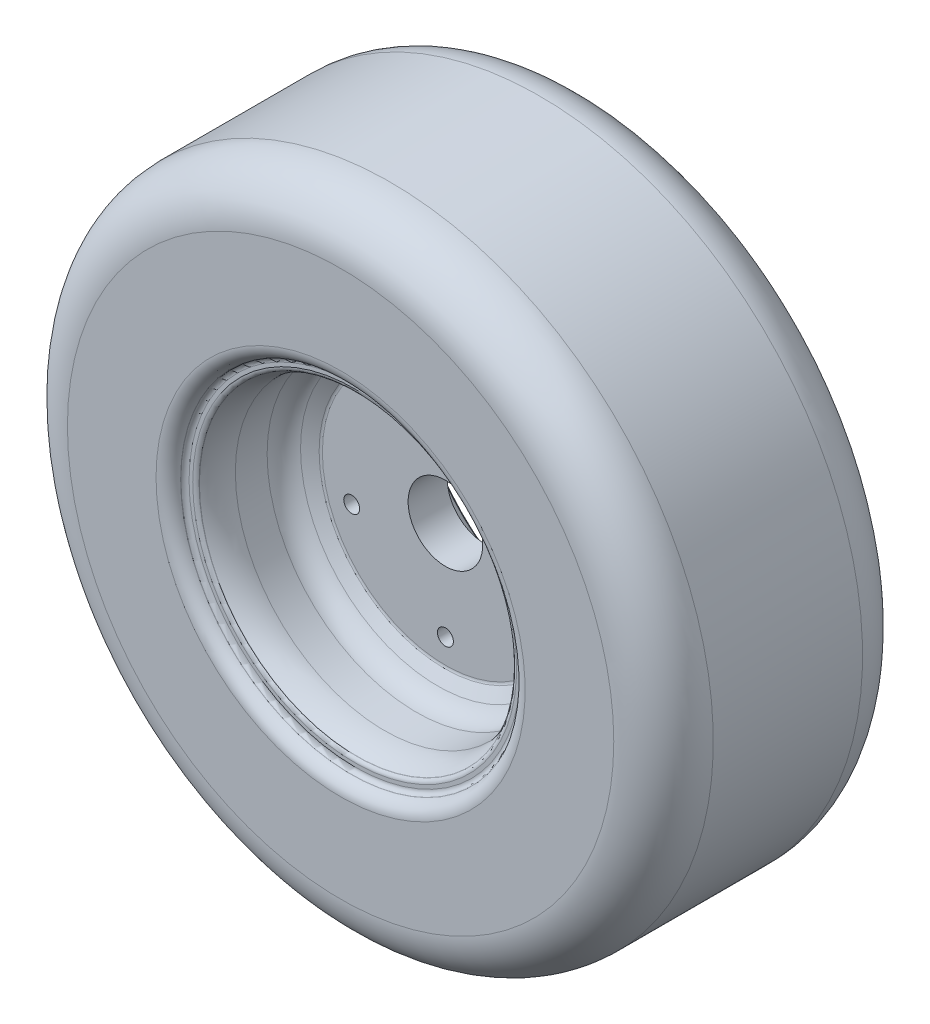
SolidWorks part; units mm, degrees
material "Rubber"
ref_plane "Front Plane" through (0, 0, 0) normal (0, 0, 1) x (1, 0, 0)
ref_plane "Top Plane" through (0, 0, 0) normal (0, 1, 0) x (1, 0, 0)
ref_plane "Right Plane" through (0, 0, 0) normal (1, 0, 0) x (0, 0, -1)
sketch "Sketch1" plane through (0, 0, 0) normal (1, 0, 0) x (0, 0, -1)
  line L0 (0, 164.846) -> (0, -164.846) construction
  line L1 (76.2, 0) -> (-76.2, 0) construction
  line L2 (10, 0) -> (10, 62.7965)
  line L3 (24.13, 164.846) -> (0, 164.846)
  line L4 (63.5, 139.446) -> (63.5, 94.2121)
  line L5 (58.1976, 86.9531) -> (58.1075, 86.9243)
  line L6 (56.34, 84.5046) -> (56.34, 82.6394)
  line L7 (55.2089, 80.526) -> (55.1189, 80.4659)
  line L8 (41.0295, 76.2) -> (24.8106, 76.2)
  line L9 (13.9205, 70.0341) -> (10.362, 64.1033)
  line L10 (-24.13, 164.846) -> (0, 164.846)
  line L11 (24.13, 164.846) -> (38.1, 164.846)
  line L13 (40.18, 161.0098) -> (-40.18, 161.0098)
  line L14 (60.5, 140.6898) -> (60.5, 100.846)
  line L15 (40.18, 80.526) -> (-40.18, 80.526)
  line L16 (-60.5, 140.6898) -> (-60.5, 100.846)
  line L24 (-24.13, 164.846) -> (-38.1, 164.846)
  line L26 (-13.9205, 70.0341) -> (-10.362, 64.1033)
  line L27 (-41.0295, 76.2) -> (-24.8106, 76.2)
  line L28 (-55.2089, 80.526) -> (-55.1189, 80.4659)
  line L29 (-56.34, 84.5046) -> (-56.34, 82.6394)
  line L30 (-58.1976, 86.9531) -> (-58.1075, 86.9243)
  line L31 (-63.5, 139.446) -> (-63.5, 94.2121)
  line L32 (-10, 0) -> (-10, 62.7965)
  line L33 (10, 0) -> (-10, 0)
  arc A0 (38.1, 164.846) -> (63.5, 139.446) centre (38.1, 139.446) cw
  arc A1 (63.5, 94.2121) -> (58.1976, 86.9531) centre (55.88, 94.2121) cw
  arc A2 (58.1075, 86.9243) -> (56.34, 84.5046) centre (58.88, 84.5046) ccw
  arc A3 (56.34, 82.6394) -> (55.2089, 80.526) centre (53.8, 82.6394) cw
  arc A4 (55.1189, 80.4659) -> (41.0295, 76.2) centre (41.0295, 101.6) cw
  arc A5 (24.8106, 76.2) -> (13.9205, 70.0341) centre (24.8106, 63.5) ccw
  arc A6 (10.362, 64.1033) -> (10, 62.7965) centre (12.54, 62.7965) ccw
  arc A7 (-10.362, 64.1033) -> (-10, 62.7965) centre (-12.54, 62.7965) cw
  arc A8 (-24.8106, 76.2) -> (-13.9205, 70.0341) centre (-24.8106, 63.5) cw
  arc A9 (-55.1189, 80.4659) -> (-41.0295, 76.2) centre (-41.0295, 101.6) ccw
  arc A10 (-56.34, 82.6394) -> (-55.2089, 80.526) centre (-53.8, 82.6394) ccw
  arc A11 (-58.1075, 86.9243) -> (-56.34, 84.5046) centre (-58.88, 84.5046) cw
  arc A12 (-63.5, 94.2121) -> (-58.1976, 86.9531) centre (-55.88, 94.2121) ccw
  arc A13 (-38.1, 164.846) -> (-63.5, 139.446) centre (-38.1, 139.446) ccw
  arc A14 (-40.18, 80.526) -> (-60.5, 100.846) centre (-40.18, 100.846) cw
  arc A15 (60.5, 100.846) -> (40.18, 80.526) centre (40.18, 100.846) cw
  arc A16 (40.18, 161.0098) -> (60.5, 140.6898) centre (40.18, 140.6898) cw
  arc A17 (-40.18, 161.0098) -> (-60.5, 140.6898) centre (-40.18, 140.6898) ccw
  point P15 (63.5, 164.846)
  point P18 (63.5, 88.646)
  point P21 (56.34, 86.36)
  point P24 (56.34, 81.28)
  point P27 (48.72, 76.2)
  point P30 (17.62, 76.2)
  point P33 (10, 63.5)
  dimension "D3" = 76.2
  dimension "D13" = 25.4
  dimension "D14" = 7.62
  dimension "D15" = 2.54
  dimension "D16" = 2.54
  dimension "D17" = 25.4
  dimension "D18" = 12.7
  dimension "D19" = 2.54
  dimension "D20" = 20.32
  dimension "D1" = 329.692
  dimension "D2" = 152.4
  dimension "D4" = 63.5
  dimension "D5" = 127
  dimension "D6" = 10
  dimension "D7" = 7.62
  dimension "D8" = 12.7
  dimension "D9" = 5.08
  dimension "D10" = 7.62
  dimension "D11" = 5.08
  dimension "D12" = 7.16
  dimension "D21" = 3
  dimension "D22" = 3
revolve "Revolve2" add sketch "Sketch1" angle 360 about L1
sketch "Sketch3" plane through (0, 0, -10) normal (0, 0, -1) x (-1, 0, 0)
  line L0 (50.292, 0) -> (-50.292, 0) construction
  line L1 (0, 50.292) -> (0, -50.292) construction
  line L2 (0, 0) -> (47.8305, -15.5411) construction
  circle A0 centre (0, 0) radius 50.292 construction
  circle A1 centre (0, -50.292) radius 4.064
  circle A2 centre (-47.8305, -15.5411) radius 4.064
  circle A3 centre (-29.5609, 40.6871) radius 4.064
  circle A4 centre (29.5609, 40.6871) radius 4.064
  circle A5 centre (47.8305, -15.5411) radius 4.064
  circle A6 centre (0, 0) radius 19.05
  point P20 (0, 0)
  dimension "D1" = 100.584
  dimension "D2" = 8.128
  dimension "D3" = 5
  dimension "D5" = 50.292
  dimension "D6" = 38.1
  dimension "D4" = 72
extrude "Cut-Extrude1" cut sketch "Sketch3" against normal through all both and the other way through all
ref_axis "Axis1" [suppressed] through (0, 0, 10) along (0, 0, -1)
ref_plane "Plane1" through (0, 167.64, 0) normal (0, 1, 0) x (1, 0, 0)
sketch "Sketch4" plane through (0, 167.64, 0) normal (0, 1, 0) x (1, 0, 0)
  line L0 (-164.846, -38.1) -> (164.846, -38.1) construction
  line L1 (-164.846, 38.1) -> (164.846, 38.1) construction
  line L3 (-6, -32.1) -> (0, -38.1)
  line L5 (-164.846, 0) -> (164.846, 0) construction
  line L6 (-24, -38.1) -> (-18, -32.1)
  line L7 (-18, -32.1) -> (-6, -32.1)
  line L8 (-164.846, 38.1) -> (-164.846, -38.1) construction
  line L9 (0, -38.1) -> (-24, -38.1)
  line L10 (164.846, -38.1) -> (164.846, 38.1) construction
  line L12 (-3, -27.1) -> (9, -27.1)
  line L13 (9, -27.1) -> (15, -21.1)
  line L14 (15, -21.1) -> (3, -13.0333)
  line L15 (3, -13.0333) -> (9, -7.0333)
  line L16 (9, -7.0333) -> (3, -1.0333)
  line L17 (3, -1.0333) -> (-9, -1.0333)
  line L22 (51, 32.1) -> (45, 38.1)
  line L24 (69, 38.1) -> (63, 32.1)
  line L25 (63, 32.1) -> (51, 32.1)
  line L26 (45, 38.1) -> (69, 38.1)
  line L27 (-9, -1.0333) -> (-15, -7.0333)
  line L28 (-15, -7.0333) -> (-3, -15.1)
  line L29 (-3, -15.1) -> (-9, -21.1)
  line L30 (-9, -21.1) -> (-3, -27.1)
  line L31 (21, -13.0333) -> (33, -13.0333)
  line L32 (33, -13.0333) -> (39, -7.0333)
  line L33 (39, -7.0333) -> (27, 1.0333)
  line L34 (27, 1.0333) -> (33, 7.0333)
  line L35 (33, 7.0333) -> (27, 13.0333)
  line L36 (27, 13.0333) -> (15, 13.0333)
  line L37 (15, 13.0333) -> (9, 7.0333)
  line L38 (9, 7.0333) -> (21, -1.0333)
  line L39 (21, -1.0333) -> (15, -7.0333)
  line L40 (15, -7.0333) -> (21, -13.0333)
  line L41 (45, 1.0333) -> (57, 1.0333)
  line L42 (57, 1.0333) -> (63, 7.0333)
  line L43 (63, 7.0333) -> (51, 15.1)
  line L44 (51, 15.1) -> (57, 21.1)
  line L45 (57, 21.1) -> (51, 27.1)
  line L46 (51, 27.1) -> (39, 27.1)
  line L47 (39, 27.1) -> (33, 21.1)
  line L48 (33, 21.1) -> (45, 13.0333)
  line L49 (45, 13.0333) -> (39, 7.0333)
  line L50 (39, 7.0333) -> (45, 1.0333)
  dimension "D1" = 5
  dimension "D2" = 12
  dimension "D3" = 6
  dimension "D5" = 6
  dimension "D6" = 5
  dimension "D7" = 15
  dimension "D8" = 3
wrap "Wrap2" [suppressed] sketch "Sketch4" source sketch "Sketch4" thickness 3 parameters "D1"=3
fillet "Fillet7" [suppressed] radius 1.5
pattern_circular "CirPattern4" [suppressed] count 18 over 360 about axis through (0, 0, 10) along (0, 0, -1) of bodies 103
sketch "Sketch5" plane through (0, 167.64, 0) normal (0, 1, 0) x (1, 0, 0)
  line L0 (-31.467, -38.1) -> (-13.1193, -17.5064)
  line L1 (-164.846, -38.1) -> (164.846, -38.1) construction
  line L3 (-13.1193, -17.5064) -> (-18.5551, -12.6634)
  line L4 (-18.5551, -12.6634) -> (-24.4139, -19.2393)
  line L5 (-24.4139, -19.2393) -> (-35.4121, -19.2393)
  line L6 (-35.4121, -19.2393) -> (-46.9005, -32.1339)
  line L7 (-46.9005, -32.1339) -> (-46.9005, -38.1)
  line L8 (-31.467, -38.1) -> (-46.9005, -38.1)
  line L10 (17.0057, 38.1) -> (0, 17.3211)
  line L11 (-164.846, 38.1) -> (164.846, 38.1) construction
  line L12 (0, 17.3211) -> (5.985, 12.423)
  line L13 (5.985, 12.423) -> (11.4487, 19.0989)
  line L14 (11.4487, 19.0989) -> (23.9498, 19.0989)
  line L15 (23.9498, 19.0989) -> (35.7487, 33.5158)
  line L16 (35.7487, 33.5158) -> (35.7487, 38.1)
  line L17 (35.7487, 38.1) -> (17.0057, 38.1)
wrap "Wrap3" [suppressed] sketch "Sketch5" source sketch "Sketch5" thickness 3 parameters "D1"=3
fillet "Fillet8" [suppressed] radius 1
pattern_circular "CirPattern5" [suppressed] count 18 over 360 about axis through (0, 0, 10) along (0, 0, -1) of bodies 103
sketch "Sketch7" [suppressed] plane through (0, 167.64, 0) normal (0, 1, 0) x (1, 0, 0)
  line L0 (0, -41.1) -> (-11.7779, -61.5)
  line L1 (-139.446, -63.5) -> (139.446, -63.5) construction
  line L2 (-11.7779, -61.5) -> (-28.7779, -61.5)
  line L3 (-28.7779, -61.5) -> (-17, -41.1)
  line L4 (-17, -41.1) -> (-11, -41.1)
  line L5 (-11, -41.1) -> (-15.0415, -48.1)
  line L6 (-6, -41.1) -> (-10.0415, -48.1)
  line L7 (-6, -41.1) -> (0, -41.1)
  line L9 (-23.916, -38.1) -> (0, -38.1) construction
  line L10 (-10.0415, -48.1) -> (-15.0415, -48.1)
  dimension "D1" = 3
  dimension "D2" = 60
  dimension "D3" = 2
  dimension "D5" = 7
  dimension "D6" = 6
  dimension "D7" = 5
extrude "Boss-Extrude3" [suppressed] add sketch "Sketch7" against normal up to surface (3.0811 mm away)
sketch "Sketch8" [suppressed] plane through (0, 167.64, 0) normal (0, 1, 0) x (1, 0, 0)
  line L0 (-12.6314, 41.1) -> (-1.4308, 60.5)
  line L1 (-1.4308, 60.5) -> (15.5692, 60.5)
  line L2 (15.5692, 60.5) -> (4.3686, 41.1)
  line L3 (4.3686, 41.1) -> (-1.6314, 41.1)
  line L4 (-1.6314, 41.1) -> (2.4101, 48.1)
  line L5 (2.4101, 48.1) -> (-2.5899, 48.1)
  line L6 (-2.5899, 48.1) -> (-6.6314, 41.1)
  line L7 (-6.6314, 41.1) -> (-12.6314, 41.1)
  line L8 (94.2121, 63.5) -> (-94.2121, 63.5) construction
  line L9 (11.4487, 38.1) -> (-12.53, 38.1) construction
  line L10 (-17, -41.1) -> (-28.7779, -61.5) construction
  dimension "D1" = 6
  dimension "D2" = 7
  dimension "D3" = 3
  dimension "D4" = 3
  dimension "D5" = 5
extrude "Boss-Extrude4" [suppressed] add sketch "Sketch8" against normal up to surface (3.1054 mm away)
fillet "Fillet5" [suppressed] radius 13
fillet "Fillet6" [suppressed] radius 3
pattern_circular "CirPattern6" [suppressed] count 36 over 360 about axis through (0, 0, 10) along (0, 0, -1) of bodies 117
